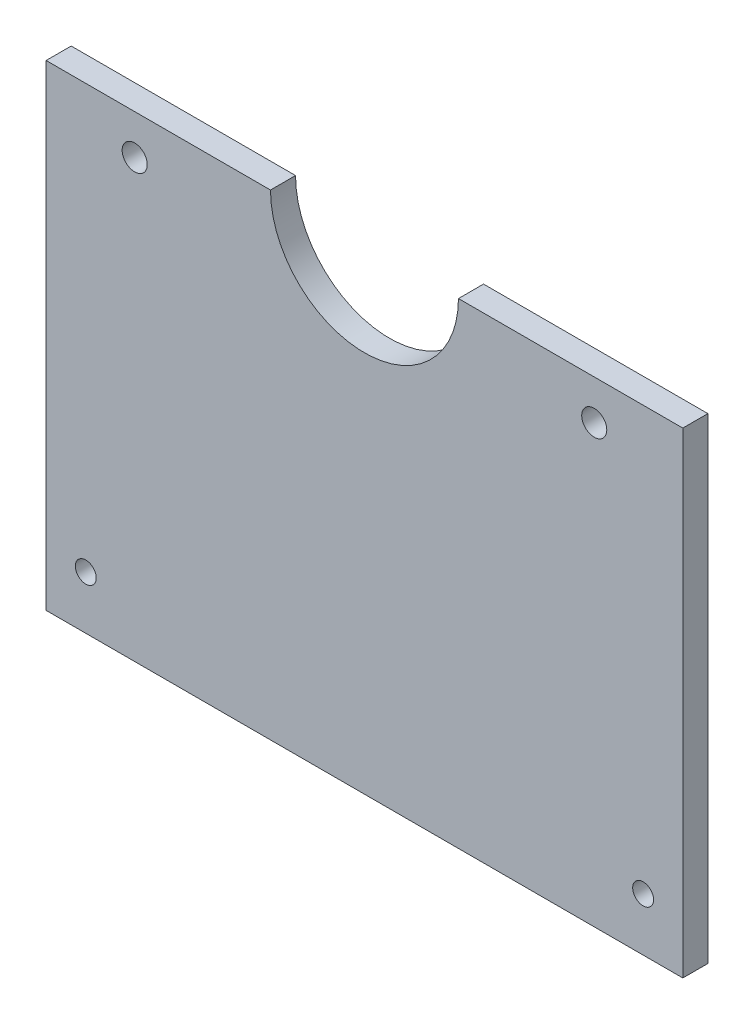
SolidWorks part; units mm, degrees
ref_plane "Front Plane" through (0, 0, 0) normal (0, 0, 1) x (1, 0, 0)
ref_plane "Top Plane" through (0, 0, 0) normal (0, 1, 0) x (1, 0, 0)
ref_plane "Right Plane" through (0, 0, 0) normal (1, 0, 0) x (0, 0, -1)
sketch "Sketch2" plane through (0, 0, 0) normal (0, 0, 1) x (1, 0, 0)
  line L0 (-55, 104.5) -> (55, 104.5) construction
  line L1 (-76.2, 0) -> (76.2, 0)
  line L2 (-76.2, 0) -> (-76.2, 114)
  line L3 (-76.2, 114) -> (76.2, 114) construction
  line L4 (76.2, 0) -> (76.2, 114)
  line L5 (0, 104.5) -> (0, 0) construction
  line L6 (0, 104.5) -> (0, 114) construction
  line L7 (0, 114) -> (-22.5, 114) construction
  line L8 (-22.5, 114) -> (-76.2, 114)
  line L9 (22.5, 114) -> (76.2, 114)
  circle A0 centre (-55, 104.5) radius 3
  circle A1 centre (55, 104.5) radius 3
  circle A2 centre (-55, 104.5) radius 16 construction
  circle A3 centre (55, 104.5) radius 16 construction
  arc A4 (-22.5, 114) -> (22.5, 114) centre (0, 114) ccw
  point P6 (0, 0)
  dimension "D1" = 6
  dimension "D2" = 32
  dimension "D5" = 45
  dimension "D3" = 110
  dimension "D4" = 9.5
  dimension "D6" = 152.4
  dimension "D7" = 104.5
extrude "Boss-Extrude1" add sketch "Sketch2" along normal mid plane 6
sketch "Sketch3" plane through (0, 0, 3) normal (0, 0, 1) x (1, 0, 0)
  line L1 (-76.2, 0) -> (-66.7, 0) construction
  line L2 (-76.2, 0) -> (-76.2, 12.7) construction
  line L3 (-76.2, 12.7) -> (-66.7, 12.7) construction
  line L4 (-66.7, 0) -> (-66.7, 12.7) construction
  line L5 (76.2, 0) -> (66.7, 0) construction
  line L6 (76.2, 0) -> (76.2, 12.7) construction
  line L7 (76.2, 12.7) -> (66.7, 12.7) construction
  line L8 (66.7, 0) -> (66.7, 12.7) construction
  circle A0 centre (-66.7, 12.7) radius 2.5
  circle A1 centre (66.7, 12.7) radius 2.5
  dimension "D1" = 12.7
  dimension "D2" = 5
  dimension "D3" = 9.5
extrude "Cut-Extrude1" cut sketch "Sketch3" against normal blind 6
